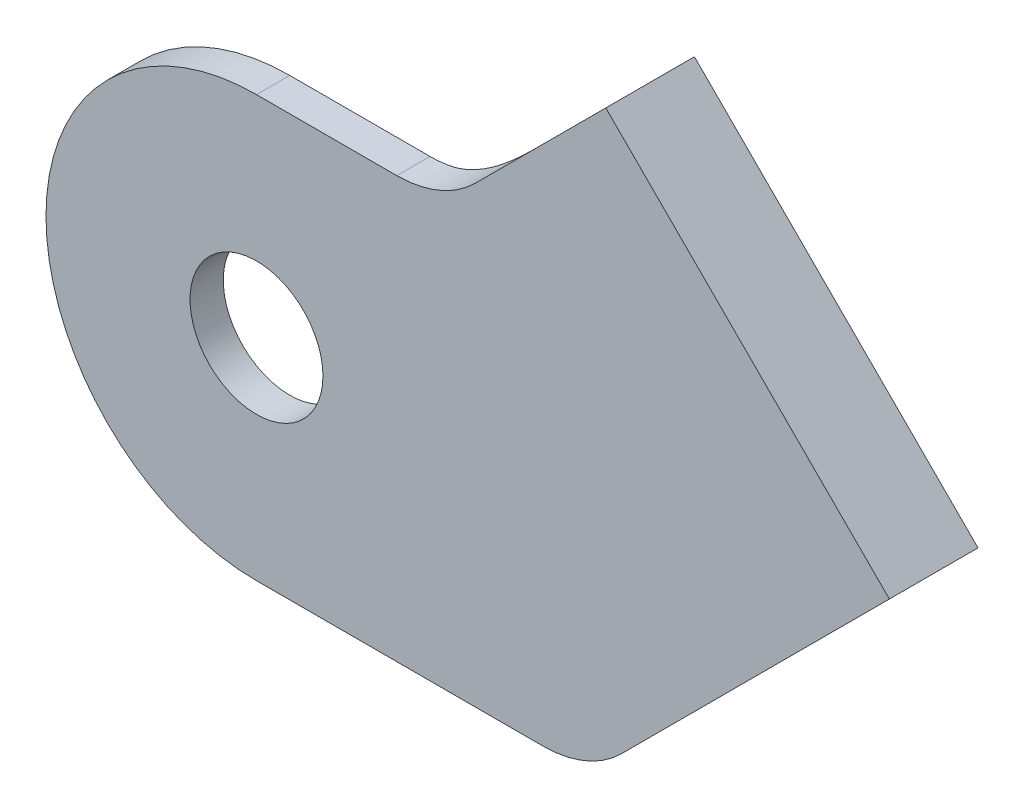
SolidWorks part; units mm, degrees
material "Foam"
ref_plane "Front Plane" through (0, 0, 0) normal (0, 0, 1) x (1, 0, 0)
ref_plane "Top Plane" through (0, 0, 0) normal (0, 1, 0) x (1, 0, 0)
ref_plane "Right Plane" through (0, 0, 0) normal (1, 0, 0) x (0, 0, -1)
sketch "Sketch1" plane through (0, 0, 0) normal (0, 0, 1) x (1, 0, 0)
  line L0 (51.4027, 28) -> (24.5327, 1.1299) construction
  line L1 (0, -19) -> (30, -19)
  line L2 (17.3202, 8.3424) -> (31.7452, -6.0825) construction
  line L3 (31.7452, -6.0825) -> (58.6152, 20.7875) construction
  line L4 (17.3202, 8.3424) -> (44.1902, 35.2125) construction
  line L5 (30, -19) -> (64.2014, 15.2014)
  line L6 (44.1902, 35.2125) -> (58.6152, 20.7875)
  line L7 (64.2014, 15.2014) -> (58.6152, 20.7875)
  line L8 (0, 0) -> (0, 28) construction
  line L9 (44.1902, 35.2125) -> (38.6041, 40.7986)
  line L10 (38.6041, 40.7986) -> (16.8055, 19)
  line L11 (16.8055, 19) -> (0, 19)
  line L12 (0, 0) -> (-19, 0) construction
  line L19 (51.4027, 28) -> (0, 28) construction
  arc A0 (0, 19) -> (0, -19) centre (0, 0) ccw
  circle A1 centre (0, 0) radius 2.5
  dimension "D1" = 38
  dimension "D5" = 30
  dimension "D6" = 5
  dimension "D14" = 45
  dimension "D2" = 20.4
  dimension "D3" = 38
  dimension "D4" = 36.2
  dimension "D13" = 28
extrude "Boss-Extrude1" add sketch "Sketch1" along normal blind 3
sketch "Sketch2" plane through (0, 0, 3) normal (0, 0, 1) x (1, 0, 0)
  line L0 (51.4027, 28) -> (31.4988, 8.0961) construction
  line L1 (64.2014, 15.2014) -> (38.6041, 40.7986) construction
  circle A0 centre (38.8781, 35.5749) radius 1.5
  circle A1 centre (58.9776, 15.4754) radius 1.5
  dimension "D1" = 3
  dimension "D2" = 3.5
  dimension "D3" = 28.425
extrude "Cut-Extrude1" cut sketch "Sketch2" against normal through all
fillet "Fillet1" radius 10 2 edges at (16.8055, 19, 1.5) (30, -19, 1.5)
sketch "Sketch3" plane through (0, 0, 3) normal (0, 0, 1) x (1, 0, 0)
  line L0 (38.6041, 40.7986) -> (31.533, 33.7276)
  line L1 (38.6041, 40.7986) -> (19.7344, 21.9289) construction
  line L2 (31.533, 33.7276) -> (57.1303, 8.1303)
  line L3 (32.9289, -16.0711) -> (64.2014, 15.2014) construction
  line L4 (57.1303, 8.1303) -> (64.2014, 15.2014)
  line L5 (64.2014, 15.2014) -> (38.6041, 40.7986)
  circle A0 centre (0, 0) radius 6
  dimension "D2" = 12
  dimension "D1" = 10
extrude "Cut-Extrude2" cut sketch "Sketch3" against normal through all
sketch "Sketch5" plane through (0, 0, 0) normal (0, 0, -1) x (-1, 0, 0)
  line L0 (-57.1303, 8.1303) -> (-31.533, 33.7276)
  line L1 (-31.533, 33.7276) -> (-20.9264, 23.121)
  line L2 (-31.533, 33.7276) -> (-19.7344, 21.9289) construction
  line L3 (-20.9264, 23.121) -> (-46.5237, -2.4763)
  line L4 (-32.9289, -16.0711) -> (-57.1303, 8.1303) construction
  line L5 (-46.5237, -2.4763) -> (-57.1303, 8.1303)
  dimension "D1" = 15
extrude "Boss-Extrude3" add sketch "Sketch5" along normal blind 5
fillet "Fillet3" radius 8 1 edges
equation "\"D2@Sketch1\"=20.20mm+\"cut_free@Parameters@Parameters.SLDPRT\""
